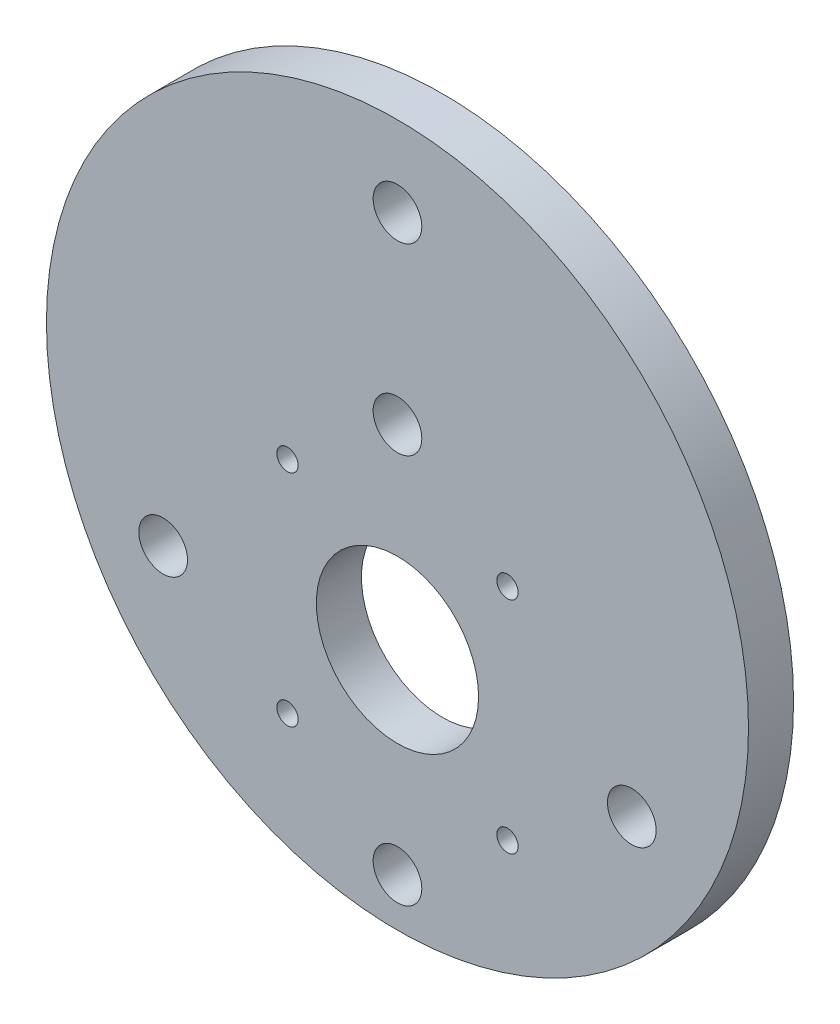
SolidWorks part; units mm, degrees
ref_plane "Front Plane" through (0, 0, 0) normal (0, 0, 1) x (1, 0, 0)
ref_plane "Top Plane" through (0, 0, 0) normal (0, 1, 0) x (1, 0, 0)
ref_plane "Right Plane" through (0, 0, 0) normal (1, 0, 0) x (0, 0, -1)
sketch "Sketch1" plane through (0, 0, 0) normal (0, 0, 1) x (1, 0, 0)
  circle A0 centre (0, 0) radius 49.4665
  dimension "D1" = 98.933
extrude "Boss-Extrude1" add sketch "Sketch1" along normal blind 6.35
sketch "Sketch2" plane through (0, 0, 6.35) normal (0, 0, 1) x (1, 0, 0)
  line L0 (-15.5, -30.74) -> (15.5, 0.26) construction
  line L1 (-15.5, 0.26) -> (15.5, 0.26)
  line L2 (-15.5, 0.26) -> (-15.5, -30.74)
  line L3 (-15.5, -30.74) -> (15.5, -30.74)
  line L4 (15.5, 0.26) -> (15.5, -30.74)
  point P4 (0, -15.24)
  point P5 (0, 0.26)
  dimension "D1" = 31
  dimension "D2" = 31
  dimension "D3" = 15.24
hole_wizard "M3 Screw Hole - Ø3.0mm Dowel Hole" positions "Sketch3" profile "Sketch4" hole size "Ø3.0" standard "ANSI Metric" end condition through all
sketch "Sketch3" plane through (0, 0, 6.35) normal (0, 0, 1) x (1, 0, 0)
  point P0 (15.5, 0.26)
  point P3 (-15.5, 0.26)
  point P6 (-15.5, -30.74)
  point P9 (15.5, -30.74)
sketch "Sketch4" plane through (15.5, 0.26, 6.35) normal (1, 0, 0) x (0, -1, 0)
  line L0 (0, 0) -> (0, 6.35)
  line L1 (0, 6.35) -> (1.5, 6.35)
  line L2 (1.5, 6.35) -> (1.5, 0)
  line L5 (1.5, 0) -> (0, 0)
  line L11 (0, -6.35) -> (0, 107.95) construction
  dimension "Thru Hole Dia." = 3
  dimension "Thru Hole Depth" = 6.35
sketch "Sketch5" plane through (0, 0, 6.35) normal (0, 0, 1) x (1, 0, 0)
  line L0 (-15.5, -30.74) -> (15.5, 0.26) construction
  line L1 (-21.209, 5.969) -> (21.209, 5.969)
  line L2 (-21.209, 5.969) -> (-21.209, -36.449)
  line L3 (-21.209, -36.449) -> (21.209, -36.449)
  line L4 (21.209, 5.969) -> (21.209, -36.449)
  line L5 (-21.209, 5.969) -> (21.209, -36.449) construction
  line L6 (-21.209, -36.449) -> (21.209, 5.969) construction
  circle A0 centre (0, -42.672) radius 3.429
  circle A1 centre (0, 12.26) radius 3.429
  point P0 (0, -15.24)
  point P7 (0, -15.24)
  dimension "D3" = 6.858
  dimension "D5" = 6.858
  dimension "D1" = 42.418
  dimension "D2" = 27.5
  dimension "D4" = 42.418
  dimension "D6" = 27.432
extrude "Cut-Extrude1" cut sketch "Sketch5" against normal through all contours A0 | A1 region at (0, -42.672, 6.35)
sketch "Sketch6" plane through (0, 0, 6.35) normal (0, 0, 1) x (1, 0, 0)
  line L0 (0, 38.1282) -> (-33.02, -19.0641) construction
  line L1 (-33.02, -19.0641) -> (33.02, -19.0641) construction
  line L2 (33.02, -19.0641) -> (0, 38.1282) construction
  line L3 (-33.02, -19.0641) -> (0, 0) construction
  line L4 (0, 0) -> (33.02, -19.0641) construction
  line L5 (0, 0) -> (0, 38.1282) construction
  circle A0 centre (0, 38.1282) radius 3.429
  circle A1 centre (-33.02, -19.0641) radius 3.429
  circle A2 centre (33.02, -19.0641) radius 3.429
  dimension "D1" = 6.858
  dimension "D2" = 66.04
  dimension "D3" = 60
  dimension "D4" = 60
extrude "Cut-Extrude2" cut sketch "Sketch6" against normal through all
sketch "Sketch7" plane through (0, 0, 6.35) normal (0, 0, 1) x (1, 0, 0)
  line L0 (-15.5, -30.74) -> (15.5, 0.26) construction
  circle A0 centre (0, -15.24) radius 11.43
  point P4 (0, -15.24)
  dimension "D1" = 22.86
extrude "Cut-Extrude3" cut sketch "Sketch7" against normal through all
